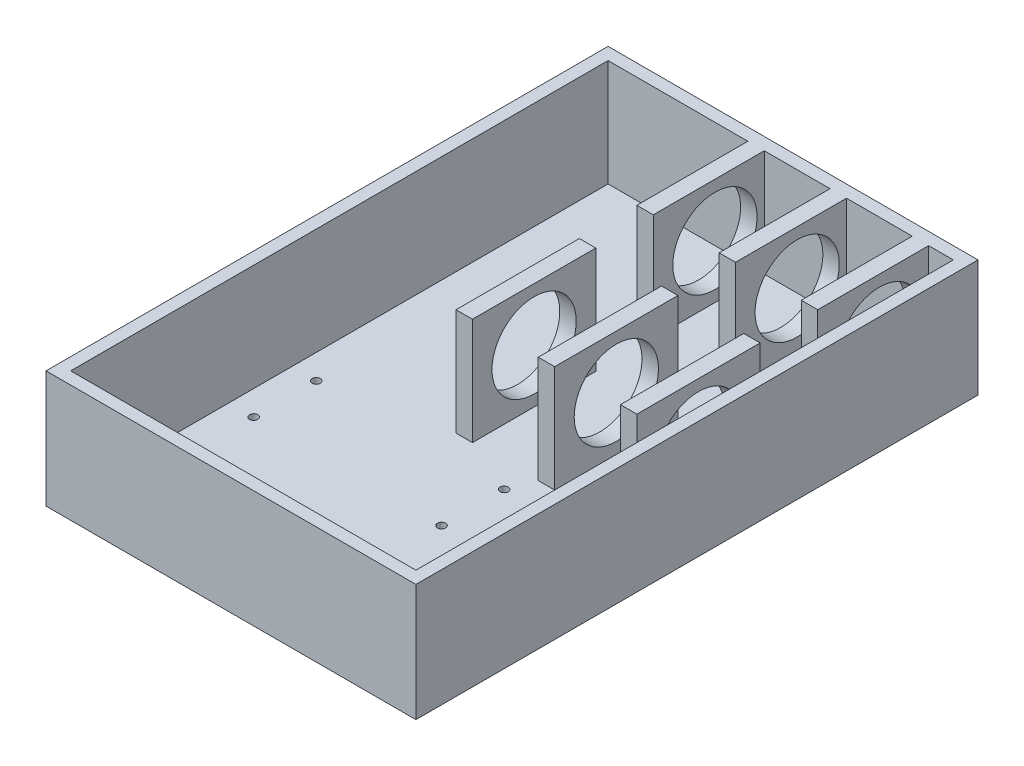
SolidWorks part; units mm, degrees
ref_plane "Front Plane" through (0, 0, 0) normal (0, 0, 1) x (1, 0, 0)
ref_plane "Top Plane" through (0, 0, 0) normal (0, 1, 0) x (1, 0, 0)
ref_plane "Right Plane" through (0, 0, 0) normal (1, 0, 0) x (0, 0, -1)
sketch "Sketch3" plane through (0, 0, 0) normal (0, 1, 0) x (1, 0, 0)
  line L1 (0, 0) -> (-90, 0)
  line L2 (0, 0) -> (0, -136.7612)
  line L3 (0, -136.7612) -> (-90, -136.7612)
  line L4 (-90, 0) -> (-90, -136.7612)
  dimension "D1" = 90
extrude "Boss-Extrude2" add sketch "Sketch3" along normal blind 2.5
sketch "Sketch4" plane through (0, 2.5, 0) normal (0, 1, 0) x (1, 0, 0)
  line L0 (-90, 0) -> (-90, -136.7612) construction
  line L1 (0, 0) -> (-90, 0) construction
  line L2 (-29, 0) -> (-29, -30)
  line L3 (-53, 0) -> (-49, 0)
  line L4 (-53, 0) -> (-53, -30)
  line L5 (-53, -30) -> (-49, -30)
  line L6 (-49, 0) -> (-49, -30)
  line L7 (-33, 0) -> (-33, -30)
  line L8 (-33, 0) -> (-29, 0)
  line L9 (-33, -30) -> (-29, -30)
  line L10 (-9, 0) -> (-9, -30)
  line L11 (-13, 0) -> (-13, -30)
  line L12 (-13, 0) -> (-9, 0)
  line L13 (-13, -30) -> (-9, -30)
  line L14 (-29, -44) -> (-29, -74)
  line L15 (-53, -44) -> (-49, -44)
  line L16 (-53, -44) -> (-53, -74)
  line L17 (-53, -74) -> (-49, -74)
  line L18 (-49, -44) -> (-49, -74)
  line L19 (-33, -44) -> (-33, -74)
  line L20 (-33, -44) -> (-29, -44)
  line L21 (-33, -74) -> (-29, -74)
  line L22 (-9, -44) -> (-9, -74)
  line L23 (-13, -44) -> (-13, -74)
  line L24 (-13, -44) -> (-9, -44)
  line L25 (-13, -74) -> (-9, -74)
  point P0 (-83, -3)
  point P1 (-3, -3)
  point P7 (-83, -23)
  point P8 (-3, -23)
  dimension "D1" = 80
  dimension "D2" = 7
  dimension "D3" = 3
  dimension "D4" = 3
  dimension "D6" = 30
  dimension "D7" = 4
  dimension "D5" = 2
  dimension "D9" = 2
extrude "Boss-Extrude3" add sketch "Sketch4" along normal blind 26
sketch "Sketch5" plane through (-53, 0, 0) normal (-1, 0, 0) x (0, 0, 1)
  circle A0 centre (15, 15.5) radius 10.25
  dimension "D1" = 20.5
extrude "Cut-Extrude1" cut sketch "Sketch5" against normal through all
sketch "Sketch6" plane through (-53, 0, 0) normal (-1, 0, 0) x (0, 0, 1)
  circle A0 centre (59, 15.5) radius 10.25
  dimension "D1" = 20.5
extrude "Cut-Extrude2" cut sketch "Sketch6" against normal through all
sketch "Sketch7" plane through (0, 2.5, 0) normal (0, 1, 0) x (1, 0, 0)
  line L69 (-3, -3) -> (-9, -3)
  line L70 (-3, -133.7612) -> (-3, -3)
  line L71 (-87, -133.7612) -> (-3, -133.7612)
  line L72 (-53, -3) -> (-87, -3)
  line L73 (-87, -3) -> (-87, -133.7612)
  line L74 (-3, -3) -> (-9, -3)
  line L75 (-3, -133.7612) -> (-3, -3)
  line L76 (-87, -133.7612) -> (-3, -133.7612)
  line L77 (-53, -3) -> (-87, -3)
  line L78 (-87, -3) -> (-87, -133.7612)
  line L85 (-13, -3) -> (-29, -3)
  line L86 (-13, -3) -> (-29, -3)
  line L87 (-33, -3) -> (-33, 0)
  line L88 (-33, -3) -> (-49, -3)
  line L89 (-33, -3) -> (-49, -3)
  line L90 (-33, 0) -> (-49, 0)
  line L91 (-13, -3) -> (-13, 0)
  line L92 (-13, 0) -> (-29, 0)
  line L93 (-29, 0) -> (-29, -3)
  line L94 (-49, 0) -> (-49, -3)
  line L115 (-53, 0) -> (-90, 0)
  line L116 (-90, 0) -> (-90, -136.7612)
  line L117 (-90, -136.7612) -> (0, -136.7612)
  line L118 (0, 0) -> (-9, 0)
  line L119 (0, -136.7612) -> (0, 0)
  line L120 (-53, 0) -> (-90, 0)
  line L121 (-90, 0) -> (-90, -136.7612)
  line L122 (-90, -136.7612) -> (0, -136.7612)
  line L123 (0, 0) -> (-9, 0)
  line L124 (0, -136.7612) -> (0, 0)
  line M21 (-13, -30) -> (-13, 0)
  line M22 (-13, 0) -> (-29, 0)
  line M23 (-29, 0) -> (-29, -30)
  line M25 (-33, -30) -> (-33, 0)
  line M26 (-33, 0) -> (-49, 0)
  line M27 (-49, 0) -> (-49, -30)
  line M29 (-53, -30) -> (-53, 0)
  line M30 (-53, 0) -> (-90, 0)
  line M31 (-90, 0) -> (-90, -136.7612)
  line M32 (-90, -136.7612) -> (0, -136.7612)
  line M33 (0, -136.7612) -> (0, 0)
  line M34 (0, 0) -> (-9, 0)
  line M35 (-9, 0) -> (-9, -30)
  dimension "D1" = 3
  dimension "D2" = 3
  dimension "D3" = 3
  dimension "D5" = 0
extrude "Boss-Extrude5" add sketch "Sketch7" along normal blind 26 contours L89 M25 M26 M27 | L78 L77 L74 L75 L76 M29 M30 M31 M32 M33 M34 M35 | L86 M21 M22 M23 region at (-6, 2.5, 1.3628) region at (-21, 2.5, 1.5) region at (-41, 2.5, 1.5)
sketch "Sketch8" plane through (0, 2.5, 0) normal (0, 1, 0) x (1, 0, 0)
  line L0 (-87, -3) -> (-87, -133.7612) construction
  circle A0 centre (-81, -80) radius 1
  circle A1 centre (-35.28, -80) radius 1
  circle A2 centre (-35.28, -95.24) radius 1
  circle A3 centre (-81, -95.24) radius 1
  point P0 (-81, -80)
  point P2 (-35.28, -80)
  point P7 (-35.28, -95.24)
  point P8 (-81, -95.24)
  dimension "D4" = 2
  dimension "D1" = 6
  dimension "D2" = 6
  dimension "D5" = 2
  dimension "D3" = 2
  dimension "D6" = 2
extrude "Cut-Extrude3" cut sketch "Sketch8" against normal through all
